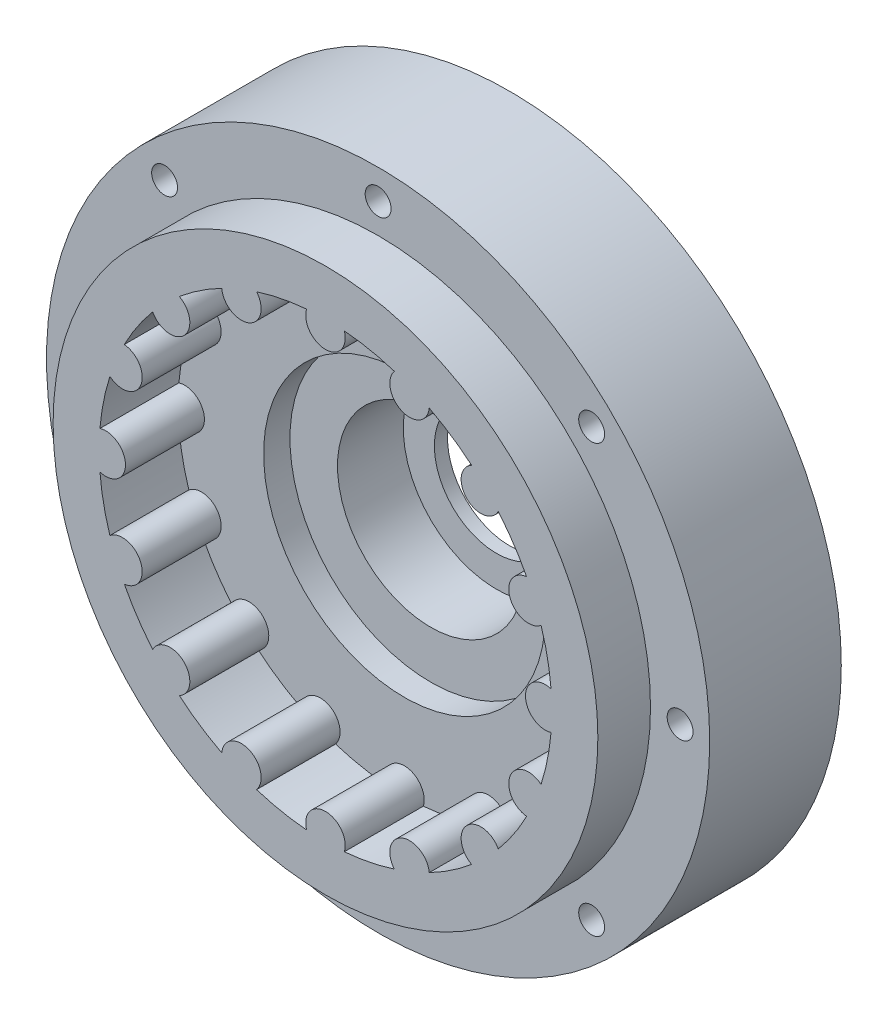
SolidWorks part; units mm, degrees
material "ABS PC"
ref_plane "Front Plane" through (0, 0, 0) normal (0, 0, 1) x (1, 0, 0)
ref_plane "Top Plane" through (0, 0, 0) normal (0, 1, 0) x (1, 0, 0)
ref_plane "Right Plane" through (0, 0, 0) normal (1, 0, 0) x (0, 0, -1)
sketch "Sketch1" plane through (0, 0, 0) normal (0, 0, 1) x (1, 0, 0)
  circle A0 centre (0, 0) radius 32.004
  dimension "D1" = 64.008
extrude "Boss-Extrude1" add sketch "Sketch1" along normal blind 12.7
sketch "Sketch2" plane through (0, 0, 12.7) normal (0, 0, 1) x (1, 0, 0)
  circle A0 centre (0, 0) radius 26.289
  circle A1 centre (0, 0) radius 32.004
  circle A2 centre (0, 0) radius 32.004
  dimension "D1" = 0
  dimension "D2" = 5.715
extrude "Cut-Extrude1" cut sketch "Sketch2" against normal blind 2.54 flip side to cut
sketch "Sketch3" plane through (0, 0, 10.16) normal (0, 0, 1) x (1, 0, 0)
  line L0 (0, 0) -> (0, 21.209) construction
  circle A1 centre (0, 21.209) radius 1.905
  circle A3 centre (0, 0) radius 21.209 construction
  circle A13 centre (8.1163, 19.5946) radius 1.905
  circle A14 centre (14.997, 14.997) radius 1.905
  circle A15 centre (19.5946, 8.1163) radius 1.905
  circle A16 centre (21.209, 0) radius 1.905
  circle A17 centre (19.5946, -8.1163) radius 1.905
  circle A18 centre (14.997, -14.997) radius 1.905
  circle A19 centre (8.1163, -19.5946) radius 1.905
  circle A20 centre (0, -21.209) radius 1.905
  circle A21 centre (-8.1163, -19.5946) radius 1.905
  circle A22 centre (-14.997, -14.997) radius 1.905
  circle A23 centre (-19.5946, -8.1163) radius 1.905
  circle A24 centre (-21.209, 0) radius 1.905
  circle A25 centre (-19.5946, 8.1163) radius 1.905
  circle A26 centre (-14.997, 14.997) radius 1.905
  circle A27 centre (-8.1163, 19.5946) radius 1.905
  dimension "D2" = 3.81
  dimension "D3" = 16
  dimension "D1" = 42.418
  dimension "D4" = 21.209
sketch "Sketch4" plane through (0, 0, 10.16) normal (0, 0, 1) x (1, 0, 0)
  circle A39 centre (0, 0) radius 27.559 construction
  circle A40 centre (0, 0) radius 13.589
  circle A41 centre (0, 0) radius 26.289 construction
  dimension "D2" = 55.118
  dimension "D1" = 13.97
extrude "Cut-Extrude3" cut sketch "Sketch4" against normal blind 2.54 contours A40 region at (0, 0, 10.16)
sketch "Sketch5" plane through (0, 0, 7.62) normal (0, 0, 1) x (1, 0, 0)
  circle A0 centre (0, 0) radius 9
  circle A1 centre (0, 0) radius 6
  dimension "D1" = 18
  dimension "D2" = 12
extrude "Cut-Extrude4" cut sketch "Sketch5" against normal through all contours A1 region at (0, 0, 7.62)
sketch "Sketch6" plane through (0, 0, 12.7) normal (0, 0, 1) x (1, 0, 0)
  line L0 (0, 0) -> (0, 32.004) construction
  line L1 (0, 0) -> (22.6302, 22.6302) construction
  line L2 (0, 0) -> (32.004, 0) construction
  line L3 (0, 0) -> (22.6302, -22.6302) construction
  line L4 (0, 0) -> (0, -32.004) construction
  line L5 (0, 0) -> (-22.6302, -22.6302) construction
  line L6 (0, 0) -> (-32.004, 0) construction
  line L7 (0, 0) -> (-22.6302, 22.6302) construction
  line L8 (0, 0) -> (0, 29.1465) construction
  circle A0 centre (0, 0) radius 32.004 construction
  point P6 (0, 29.1465)
  point P16 (20.6097, 20.6097)
  point P18 (29.1465, 0)
  point P20 (20.6097, -20.6097)
  point P22 (0, -29.1465)
  point P24 (-20.6097, -20.6097)
  point P26 (-29.1465, 0)
  point P28 (-20.6097, 20.6097)
  dimension "D1" = 29.1465
  dimension "D2" = 8
hole_wizard "M3x0.5 Tapped Hole1" positions "Sketch6" profile "Sketch7" tap size "M3x0.5" standard "ANSI Metric" end condition through all
sketch "Sketch7" plane through (-20.6097, 20.6097, 12.7) normal (1, 0, 0) x (0, -1, 0)
  line L0 (0, 0) -> (0, 12.7)
  line L1 (0, 12.7) -> (1.25, 12.7)
  line L2 (1.25, 12.7) -> (1.25, 0)
  line L5 (1.25, 0) -> (0, 0)
  line L11 (0, -6.35) -> (0, 107.95) construction
  dimension "Thru Tap Drill Dia." = 2.5
  dimension "Thru Tap Drill Depth" = 12.7
cosmetic thread "Hole Thread1" parameters "D2"=3
cosmetic thread "Hole Thread2" parameters "D2"=3
cosmetic thread "Hole Thread3" parameters "D2"=3
cosmetic thread "Hole Thread4" parameters "D2"=3
cosmetic thread "Hole Thread5" parameters "D2"=3
cosmetic thread "Hole Thread6" parameters "D2"=3
cosmetic thread "Hole Thread7" parameters "D2"=3
cosmetic thread "Hole Thread8" parameters "D2"=3
extrude "Cut-Extrude5" cut sketch "Sketch5<3>" against normal blind 6.35
sketch "Sketch5<3>" plane through (0, 0, 7.62) normal (0, 0, 1) x (1, 0, 0) same geometry as "Sketch5"
sketch "Sketch8" plane through (0, 0, 10.16) normal (0, 0, 1) x (1, 0, 0)
  circle A0 centre (0, 0) radius 26.289 construction
  circle A1 centre (0, 0) radius 26.289
  circle A2 centre (0, 0) radius 21.844
  dimension "D1" = 4.445
extrude "Boss-Extrude2" add sketch "Sketch8" along normal blind 7.62
extrude "Boss-Extrude3" add sketch "Sketch3" along normal blind 7.62
